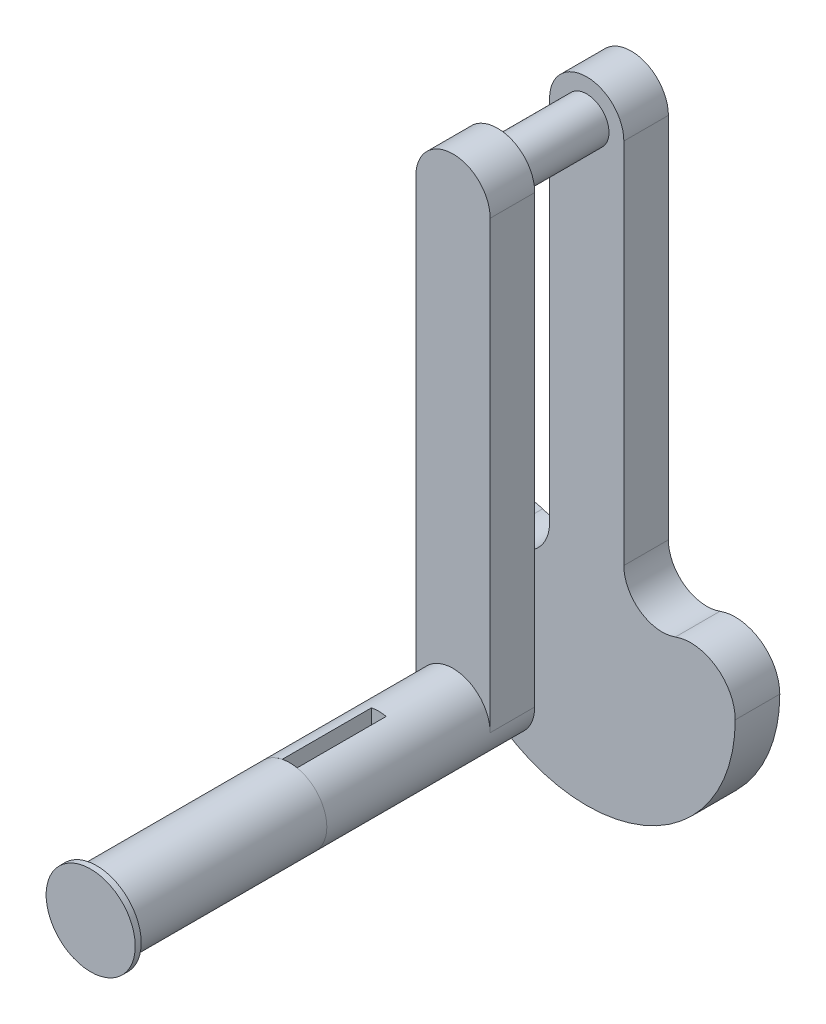
SolidWorks part; units mm, degrees
material "6061 Alloy"
ref_plane "Front Plane" through (0, 0, 0) normal (0, 0, 1) x (1, 0, 0)
ref_plane "Top Plane" through (0, 0, 0) normal (0, 1, 0) x (1, 0, 0)
ref_plane "Right Plane" through (0, 0, 0) normal (1, 0, 0) x (0, 0, -1)
sketch "Sketch2" plane through (0, 0, 0) normal (0, 0, 1) x (1, 0, 0)
  line L0 (-2.5, 12.2474) -> (2.5, 12.2474) construction
  line L1 (-2.5, 12.2474) -> (-2.5, 7.2474)
  line L2 (-2.5, 7.2474) -> (2.5, 7.2474)
  line L3 (2.5, 7.2474) -> (2.5, 12.2474)
  line L4 (0, 12.5) -> (0, 12.2474)
  circle A0 centre (0, 0) radius 12.5
  point P6 (0, 12.5)
  dimension "D1" = 25
  dimension "D2" = 5
  dimension "D3" = 5
extrude "Boss-Extrude1" add sketch "Sketch2" against normal blind 55 from offset 30 contours L1 A0 L3 L2 region at (0, -0.5464, 0)
sketch "Sketch3" plane through (0, 0, -25) normal (0, 0, -1) x (-1, 0, 0)
  line L0 (-12.5, 0) -> (-12.5, 150)
  line L1 (12.5, 0) -> (12.5, 150)
  line L5 (2.5, 12.2474) -> (2.5, 7.2474)
  line L6 (-2.5, 7.2474) -> (-2.5, 12.2474)
  line L7 (2.5, 7.2474) -> (-2.5, 7.2474)
  arc A1 (-2.5, 12.2474) -> (2.5, 12.2474) centre (0, 0) ccw construction
  arc A2 (-12.5, 150) -> (12.5, 150) centre (0, 150) cw
  arc A4 (-2.5, 12.2474) -> (2.5, 12.2474) centre (0, 0) ccw
  arc A5 (-12.5, 0) -> (12.5, 0) centre (0, 0) ccw
  dimension "D1" = 150
  dimension "D2" = 0
extrude "Boss-Extrude3" add sketch "Sketch3" along normal blind 15
sketch "Sketch5" plane through (0, 0, -40) normal (0, 0, -1) x (-1, 0, 0)
  circle A0 centre (0, 150) radius 7.5
  dimension "D1" = 15
extrude "Boss-Extrude4" add sketch "Sketch5" along normal blind 30
sketch "Sketch6" plane through (0, 0, -70) normal (0, 0, -1) x (-1, 0, 0)
  line L0 (12.5, 150) -> (12.5, 0)
  line L1 (-12.5, 150) -> (-12.5, 0)
  arc A0 (-12.5, 150) -> (12.5, 150) centre (0, 150) cw
  arc A1 (12.5, 150) -> (-12.5, 150) centre (0, 150) ccw construction
  arc A2 (12.5, 0) -> (-12.5, 0) centre (0, 0) cw
extrude "Boss-Extrude5" add sketch "Sketch6" along normal blind 15
sketch "Sketch8" plane through (0, 0, -70) normal (0, 0, -1) x (-1, 0, 0)
  line L0 (12.5, 0) -> (12.5, 150) construction
  line L1 (50, 0) -> (-50, 0) construction
  line L2 (-12.5, 26.2396) -> (12.5, 26.2396) construction
  line L3 (0, 26.2396) -> (0, 0) construction
  line L4 (-12.5, 150) -> (-12.5, 0) construction
  arc A1 (50, 0) -> (-50, 0) centre (0, 0) cw
  arc A2 (-50, 0) -> (-29.8605, 14.092) centre (-35, 0) cw
  arc A3 (-29.8605, 14.092) -> (-12.5, 26.2396) centre (-25.4302, 26.2396) ccw
  arc A5 (12.5, 26.2396) -> (29.8605, 14.092) centre (25.4302, 26.2396) ccw
  arc A6 (29.8605, 14.092) -> (50, 0) centre (35, 0) cw
  arc A7 (-12.5, 26.2396) -> (12.5, 26.2396) centre (0, 26.2396) cw
  point P18 (0, 0)
  dimension "D1" = 15
  dimension "D4" = 15
  dimension "D2" = 50
extrude "Boss-Extrude7" add sketch "Sketch8" along normal up to surface (15 mm away) up to face at (0, 75, -85)
sketch "Sketch10" plane through (0, 0, -85) normal (0, 0, -1) x (-1, 0, 0)
  line L0 (0, 0) -> (0, 50) construction
  line L1 (0, 0) -> (33.8074, -9.0587) construction
  circle A0 centre (33.8074, -9.0587) radius 6
  circle A1 centre (33.8074, -9.0587) radius 5
  dimension "D1" = 10
  dimension "D4" = 12
  dimension "D2" = 105
  dimension "D3" = 35
sketch "Sketch12" plane through (0, 0, 30) normal (0, 0, 1) x (1, 0, 0)
  circle A0 centre (0, 0) radius 12.5
extrude "Boss-Extrude8" add sketch "Sketch12" along normal blind 65
sketch "Sketch14" plane through (0, 0, 95) normal (0, 0, 1) x (1, 0, 0)
  circle A0 centre (0, 0) radius 15
  dimension "D1" = 30
extrude "Boss-Extrude9" add sketch "Sketch14" along normal blind 2
extrude "Boss-Extrude10" add sketch "Sketch2<5>" against normal blind 30 contours L1 A0 L3 L2 | L0 L1 L2 L3 | L4 L0 A0 | A0 region at (0, 9.7474, 0) region at (0, -0.5464, 0) region at (0.9388, 12.3486, 0)
sketch "Sketch2<5>" plane through (0, 0, 0) normal (0, 0, 1) x (1, 0, 0) same geometry as "Sketch2"
extrude "Boss-Extrude11" add sketch "Sketch10" along normal blind 15 contours A1 region at (-33.8074, -9.0587, -85)
extrude "Boss-Extrude12" add sketch "Sketch10<3>" along normal blind 2 from offset 15 contours A0 A1 | A1 region at (-27.9771, -9.0587, -85) region at (-33.8074, -9.0587, -85)
sketch "Sketch10<3>" plane through (0, 0, -85) normal (0, 0, -1) x (-1, 0, 0) same geometry as "Sketch10"
